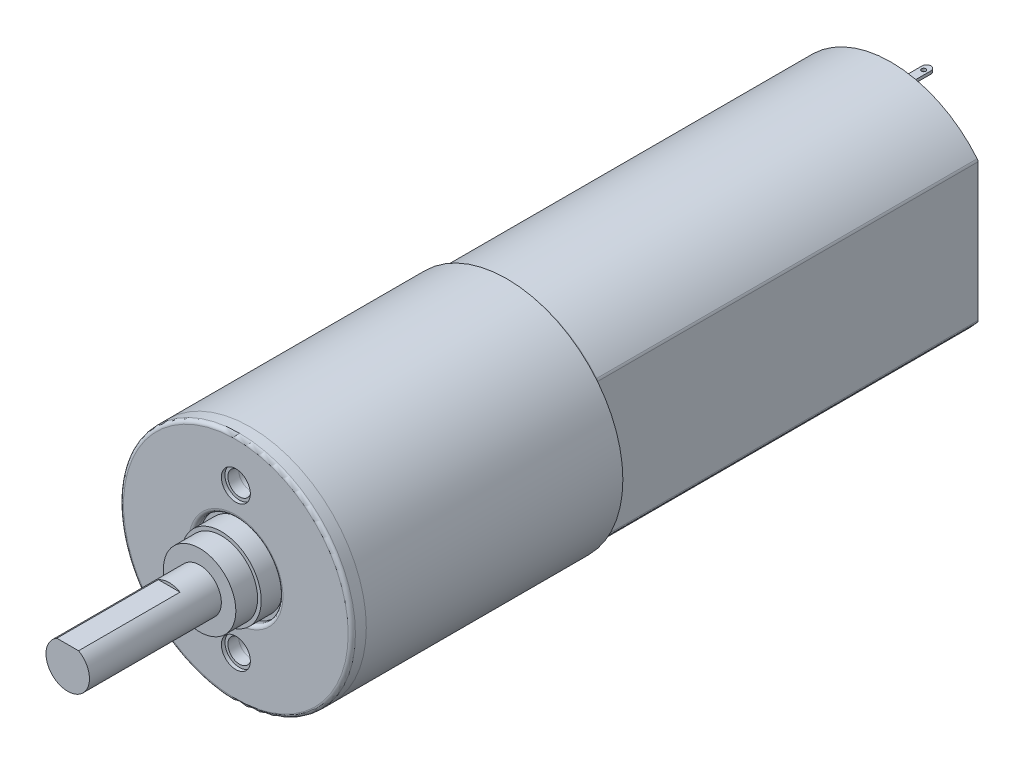
SolidWorks part; units mm, degrees
material "AISI 1035 鋼 (SS)"
ref_plane "前基準面" through (0, 0, 0) normal (0, 0, 1) x (1, 0, 0)
ref_plane "上基準面" through (0, 0, 0) normal (0, 1, 0) x (1, 0, 0)
ref_plane "右基準面" through (0, 0, 0) normal (1, 0, 0) x (0, 0, -1)
sketch "草圖1" plane through (0, 0, 0) normal (0, 0, 1) x (1, 0, 0)
  circle A0 centre (0, 0) radius 7.7
  dimension "D1" = 15.4
extrude "填料-伸長1" add sketch "草圖1" along normal blind 26.5
sketch "草圖2" plane through (0, 0, 26.5) normal (0, 0, 1) x (1, 0, 0)
  line L0 (-6, 4.826) -> (-6, -4.826)
  line L1 (6, 4.826) -> (6, -4.826)
  circle A0 centre (0, 0) radius 7.7 construction
  arc A1 (-6, 4.826) -> (-6, -4.826) centre (0, 0) ccw
  arc A2 (6, 4.826) -> (6, -4.826) centre (0, 0) cw
  circle M3 centre (0, 0) radius 7.7
  dimension "D1" = 12
extrude "除料-伸長1" cut sketch "草圖2" against normal through all contours L0 M3 | L1 M3 region at (-6.6869, 0, 26.5) region at (6.6869, 0, 26.5)
fillet "圓角1" radius 0.25 8 edges at (6, -4.826, 13.25) (6, 4.826, 13.25) (-6, 4.826, 13.25) (-6, -4.826, 13.25) (6, 0, 26.5) (0, -7.7, 26.5) (-6, 0, 26.5) (0, 7.7, 26.5)
sketch "草圖4" plane through (0, 0, 26.5) normal (0, 0, 1) x (1, 0, 0)
  circle A0 centre (0, 0) radius 8
  dimension "D1" = 16
extrude "填料-伸長2" add sketch "草圖4" along normal blind 17.7
sketch "草圖5" plane through (0, 0, 44.2) normal (0, 0, 1) x (1, 0, 0)
  circle A1 centre (0, 0) radius 8
  circle A2 centre (0, 0) radius 8
  dimension "D1" = 0
extrude "填料-伸長3" add sketch "草圖5" along normal blind 1 separate body
sketch "草圖6" plane through (0, 0, 45.2) normal (0, 0, 1) x (1, 0, 0)
  circle A0 centre (0, 0) radius 3
  circle A1 centre (0, 0) radius 8 construction
  point P3 (0, 0)
  point P4 (0, -4.5194)
  dimension "D1" = 6
extrude "除料-伸長2" cut sketch "草圖6" against normal blind 0.5
fillet "圓角3" radius 0.25 2 edges at (8, 0, 45.2) (3, 0, 45.2)
sketch "草圖7" plane through (0, 0, 44.7) normal (0, 0, 1) x (1, 0, 0)
  circle A0 centre (0, 0) radius 2.75
  dimension "D1" = 5.5
extrude "填料-伸長4" add sketch "草圖7" along normal blind 1.5
sketch "草圖8" plane through (0, 0, 46.2) normal (0, 0, 1) x (1, 0, 0)
  circle A0 centre (0, 0) radius 2.5
  dimension "D1" = 5
extrude "填料-伸長5" add sketch "草圖8" along normal blind 1.5 separate body
sketch "草圖9" plane through (0, 0, 47.7) normal (0, 0, 1) x (1, 0, 0)
  circle A0 centre (0, 0) radius 1.5
  dimension "D1" = 3
extrude "填料-伸長6" add sketch "草圖9" along normal blind 9.1
sketch "草圖10" plane through (0, 0, 56.8) normal (0, 0, 1) x (1, 0, 0)
  line L0 (-0.7483, 1.3) -> (0.7483, 1.3)
  circle A1 centre (0, 0) radius 1.5 construction
  circle A2 centre (0, 0) radius 1.5 construction
  arc A3 (-0.7483, 1.3) -> (0.7483, 1.3) centre (0, 0) cw
  circle M2 centre (0, 0) radius 1.5
  dimension "D1" = 1.3
extrude "除料-伸長3" cut sketch "草圖10" against normal blind 7 contours L0 M2 region at (0, 1.3805, 56.8)
hole_wizard "M2x0.4 螺紋孔1" positions "草圖13" profile "草圖15" tap size "M2x0.4" standard "Ansi Metric"
sketch "草圖13" plane through (0, 0, 45.2) normal (0, 0, 1) x (1, 0, 0)
  line L0 (0, -5) -> (0, 5) construction
  point P1 (0, -5)
  point P2 (0, 5)
  dimension "D1" = 10
sketch "草圖15" plane through (0, -5, 45.2) normal (1, 0, 0) x (0, -1, 0)
  line L0 (0, 0) -> (0, 3.4807)
  line L1 (0, 3.4807) -> (0.8, 3)
  line L2 (0.8, 3) -> (0.8, 0)
  line L5 (0.8, 0) -> (0, 0)
  line L10 (0, 3.4807) -> (-0.8, 3) construction
  line L11 (0, -6.35) -> (0, 107.95) construction
  dimension "螺孔鑽直徑" = 1.6
  dimension "螺孔鑽深度" = 3
  dimension "導頭角度" = 118
sketch "草圖16" plane through (0, 0, 45.2) normal (0, 0, 1) x (1, 0, 0)
  circle A0 centre (0, -5) radius 1
  circle A1 centre (0, 5) radius 1
  dimension "D1" = 2
extrude "除料-伸長4" cut sketch "草圖16" against normal blind 0.25
sketch "草圖17" plane through (0, 0, 0) normal (0, 0, -1) x (-1, 0, 0)
  line L0 (-5.75, 4.632) -> (-5.75, -4.632)
  line L1 (5.75, -4.632) -> (5.75, 4.632)
  line L2 (-5.75, 0) -> (5.75, 0) construction
  line L3 (-5.9853, 4.8215) -> (5.9853, -4.8215) construction
  line L4 (5.9853, 4.8215) -> (-5.9853, -4.8215) construction
  arc A0 (-5.75, 4.632) -> (5.75, 4.632) centre (0, 0) cw
  arc A1 (-5.943, 4.8961) -> (-6, 4.7371) centre (-5.75, 4.7371) ccw construction
  arc A2 (5.943, -4.8961) -> (6, -4.7371) centre (5.75, -4.7371) ccw construction
  arc A3 (6, 4.7371) -> (5.943, 4.8961) centre (5.75, 4.7371) ccw construction
  arc A4 (-6, -4.7371) -> (-5.943, -4.8961) centre (-5.75, -4.7371) ccw construction
  arc A5 (-5.75, -4.632) -> (5.75, -4.632) centre (0, 0) ccw
  dimension "D1" = 11.5
extrude "除料-伸長5" cut sketch "草圖17" against normal blind 0.75 contours L0 A5 L1 A0 region at (0, 0, 0)
sketch "草圖18" plane through (0, 0, 0.75) normal (0, 0, -1) x (-1, 0, 0)
  circle A0 centre (0, 0) radius 2.5
  dimension "D1" = 5
extrude "填料-伸長7" add sketch "草圖18" along normal blind 2.5
fillet "圓角4" radius 0.25 1 edges at (-2.5, 0, -1.75)
sketch "草圖19" plane through (0, 0, 0.75) normal (0, 0, -1) x (-1, 0, 0)
  line L0 (0, 0) -> (0, 6) construction
  circle A0 centre (0, 6) radius 0.5
  circle A1 centre (0, 0) radius 2.5 construction
  dimension "D1" = 6
  dimension "D2" = 1
extrude "填料-伸長8" add sketch "草圖19" along normal blind 0.5
sketch "草圖20" plane through (0, 0, 0.25) normal (0, 0, -1) x (-1, 0, 0)
  line L1 (-0.3, 5.9) -> (0.3, 5.9)
  line L2 (-0.3, 5.9) -> (-0.3, 6.1)
  line L3 (-0.3, 6.1) -> (0.3, 6.1)
  line L4 (0.3, 5.9) -> (0.3, 6.1)
  line L5 (-0.3, 5.9) -> (0.3, 6.1) construction
  line L6 (-0.3, 6.1) -> (0.3, 5.9) construction
  point P0 (0, 6)
  dimension "D1" = 0.2
  dimension "D2" = 0.6
extrude "填料-伸長9" add sketch "草圖20" along normal blind 3
sketch "草圖21" plane through (0, 5.9, 0) normal (0, -1, 0) x (1, 0, 0)
  line L0 (0.3, -2.75) -> (-0.3, -2.75) construction
  line L1 (0, 0) -> (0, -2.25) construction
  circle A0 centre (0, -2.25) radius 0.15
  dimension "D1" = 0.3
  dimension "D2" = 0.5
extrude "除料-伸長6" cut sketch "草圖21" against normal through all
fillet "圓角5" radius 0.3 2 edges at (-0.3, 6, -2.75) (0.3, 6, -2.75)
pattern_circular "環狀複製排列1" count 2 over 360 about axis through (0, 0, -1.75) along (0, 0, 1) of "填料-伸長9", "填料-伸長8", "除料-伸長6", "圓角5" reverse direction yes
